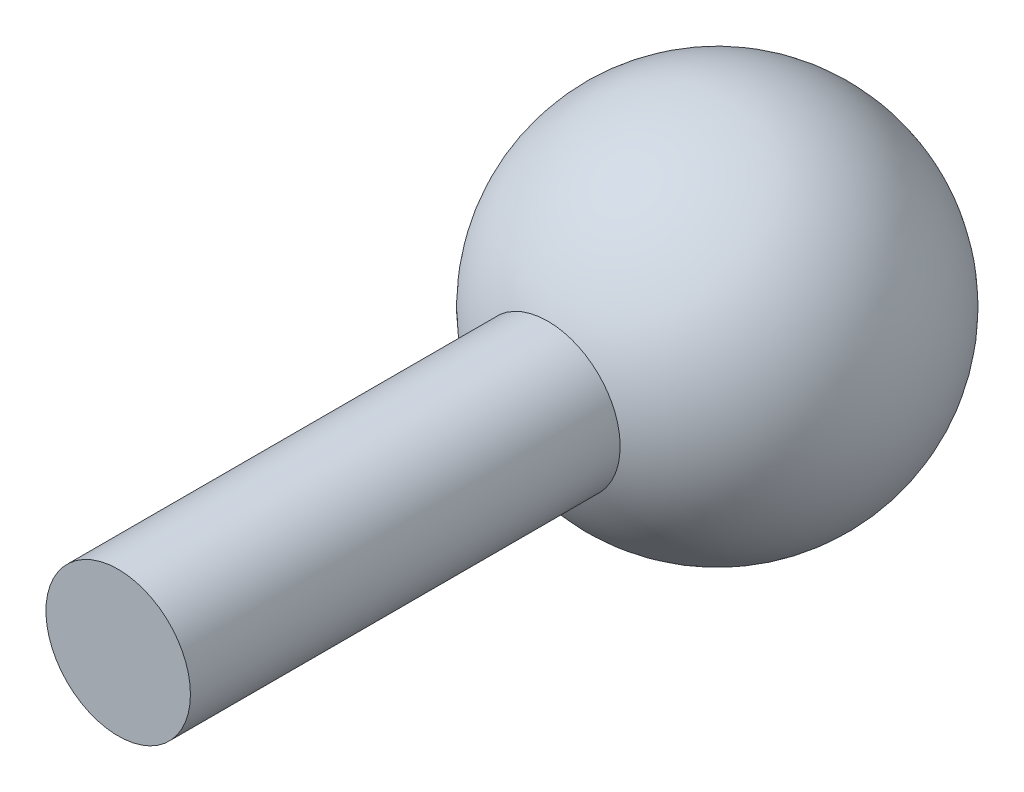
SolidWorks part; units mm, degrees
note: The reader was unsure of these and kept them because the rebuilt part matched: shared geometry of "Sketch2<9>".
ref_plane "Front Plane" through (0, 0, 0) normal (0, 0, 1) x (1, 0, 0)
ref_plane "Top Plane" through (0, 0, 0) normal (0, 1, 0) x (1, 0, 0)
ref_plane "Right Plane" through (0, 0, 0) normal (1, 0, 0) x (0, 0, -1)
sketch "Sketch1" plane through (0, 0, 0) normal (0, 0, 1) x (1, 0, 0)
  circle A0 centre (0, 0) radius 20
  dimension "D1" = 40
extrude "Boss-Extrude1" add sketch "Sketch1" along normal blind 130
sketch "Sketch2" plane through (0, 0, 0) normal (0, 1, 0) x (1, 0, 0)
  line L0 (0, 0) -> (0, 71.7161) construction
  line L1 (0, 114.3818) -> (0, -33.2604) construction
  line L2 (0, 97.5597) -> (0, 0) construction
  line L3 (0, 86.8911) -> (0, -15.175)
  circle A0 centre (0, 35.8581) radius 41.0585
  arc A2 (0, 86.8911) -> (0, -15.175) centre (0, 35.8581) ccw
  point P10 (0, 0)
extrude "Boss-Extrude2" add sketch "Sketch2" along normal mid plane 40
sketch "Sketch8" plane through (0, 20, 0) normal (0, 1, 0) x (1, 0, 0)
  circle A0 centre (0, 35.8581) radius 20
  dimension "D1" = 40
extrude "Cut-Extrude1" cut sketch "Sketch8" against normal blind 40 contours A0
sketch "Sketch15" plane through (0, 20, 0) normal (0, 1, 0) x (1, 0, 0)
revolve "Revolve5" add sketch "Sketch2<9>" angle 360 about L3
sketch "Sketch2<9>" plane through (0, 0, 0) normal (0, 1, 0) x (1, 0, 0) same geometry as "Sketch2"
